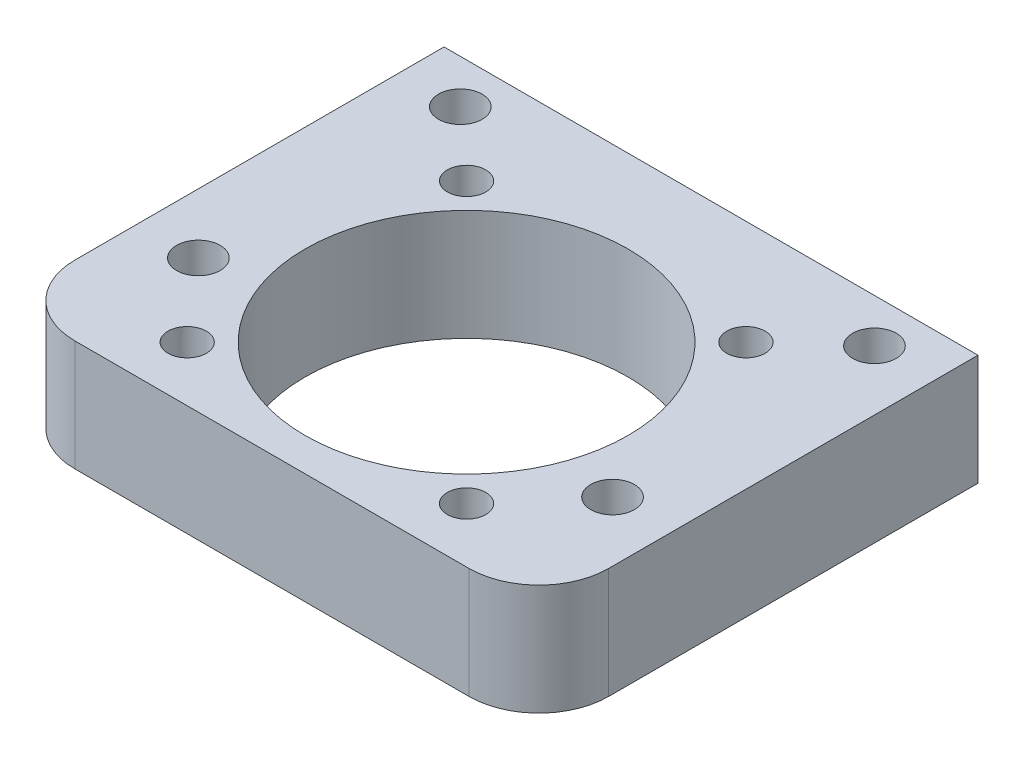
SolidWorks part; units mm, degrees
ref_plane "Front" through (0, 0, 0) normal (0, 0, 1) x (1, 0, 0)
ref_plane "Top" through (0, 0, 0) normal (0, 1, 0) x (1, 0, 0)
ref_plane "Right" through (0, 0, 0) normal (1, 0, 0) x (0, 0, -1)
ref_plane "Plane1" through (0, 6.35, 0) normal (0, 1, 0) x (1, 0, 0)
sketch "Sketch1" plane through (0, 6.35, 0) normal (0, 1, 0) x (1, 0, 0)
  line L0 (15.289, -7.15) -> (15.289, 14)
  line L1 (15.289, 14) -> (-15.289, 14)
  line L2 (-15.289, 14) -> (-15.289, -7.15)
  line L3 (-11.289, -11.15) -> (11.289, -11.15)
  arc A0 (11.289, -11.15) -> (15.289, -7.15) centre (11.289, -7.15) ccw
  arc A1 (-15.289, -7.15) -> (-11.289, -11.15) centre (-11.289, -7.15) ccw
extrude "Boss-Extrude1" add sketch "Sketch1" against normal blind 6.35
hole_wizard "Ø2.2 (2.2) Diameter Hole1" positions "Sketch3" profile "Sketch2" hole size "Ø2.2" standard "ANSI Metric"
sketch "Sketch3" plane through (0, 0, 0) normal (0, -1, 0) x (-1, 0, 0)
  point P0 (-8, -8)
sketch "Sketch2" plane through (8, 0, 8) normal (1, 0, 0) x (0, 0, -1)
  line L0 (0, 0) -> (0, 6.35)
  line L1 (0, 6.35) -> (1.1, 6.35)
  line L2 (1.1, 6.35) -> (1.1, 0)
  line L5 (1.1, 0) -> (0, 0)
  line L11 (0, -6.35) -> (0, 107.95) construction
  dimension "Thru Hole Dia." = 2.2
  dimension "Thru Hole Depth" = 6.35
hole_wizard "Ø2.2 (2.2) Diameter Hole2" positions "Sketch5" profile "Sketch4" hole size "Ø2.2" standard "ANSI Metric"
sketch "Sketch5" plane through (0, 0, 0) normal (0, -1, 0) x (-1, 0, 0)
  point P0 (8, 8)
sketch "Sketch4" plane through (-8, 0, -8) normal (1, 0, 0) x (0, 0, -1)
  line L0 (0, 0) -> (0, 6.35)
  line L1 (0, 6.35) -> (1.1, 6.35)
  line L2 (1.1, 6.35) -> (1.1, 0)
  line L5 (1.1, 0) -> (0, 0)
  line L11 (0, -6.35) -> (0, 107.95) construction
  dimension "Thru Hole Dia." = 2.2
  dimension "Thru Hole Depth" = 6.35
hole_wizard "Ø2.2 (2.2) Diameter Hole3" positions "Sketch7" profile "Sketch6" hole size "Ø2.2" standard "ANSI Metric"
sketch "Sketch7" plane through (0, 0, 0) normal (0, -1, 0) x (-1, 0, 0)
  point P0 (-8, 8)
sketch "Sketch6" plane through (8, 0, -8) normal (1, 0, 0) x (0, 0, -1)
  line L0 (0, 0) -> (0, 6.35)
  line L1 (0, 6.35) -> (1.1, 6.35)
  line L2 (1.1, 6.35) -> (1.1, 0)
  line L5 (1.1, 0) -> (0, 0)
  line L11 (0, -6.35) -> (0, 107.95) construction
  dimension "Thru Hole Dia." = 2.2
  dimension "Thru Hole Depth" = 6.35
hole_wizard "Ø2.2 (2.2) Diameter Hole4" positions "Sketch19" profile "Sketch18" hole size "Ø2.2" standard "ANSI Metric"
sketch "Sketch19" plane through (0, 6.35, 0) normal (0, 1, 0) x (1, 0, 0)
  point P0 (-8, -8)
sketch "Sketch18" plane through (-8, 6.35, 8) normal (1, 0, 0) x (0, 0, 1)
  line L0 (0, 0) -> (0, 6.35)
  line L1 (0, 6.35) -> (1.1, 6.35)
  line L2 (1.1, 6.35) -> (1.1, 0)
  line L5 (1.1, 0) -> (0, 0)
  line L11 (0, -6.35) -> (0, 107.95) construction
  dimension "Thru Hole Dia." = 2.2
  dimension "Thru Hole Depth" = 6.35
hole_wizard "Ø18.5 (18.5) Diameter Hole1" positions "Sketch9" profile "Sketch8" hole size "Ø18.5" standard "ANSI Metric"
sketch "Sketch9" plane through (0, 0, 0) normal (0, -1, 0) x (-1, 0, 0)
  point P0 (0, 0)
sketch "Sketch8" plane through (0, 0, 0) normal (1, 0, 0) x (0, 0, -1)
  line L0 (0, 0) -> (0, 6.35)
  line L1 (0, 6.35) -> (9.25, 6.35)
  line L2 (9.25, 6.35) -> (9.25, 0)
  line L5 (9.25, 0) -> (0, 0)
  line L11 (0, -6.35) -> (0, 107.95) construction
  dimension "Thru Hole Dia." = 18.5
  dimension "Thru Hole Depth" = 6.35
hole_wizard "M3 Tapped Hole1" positions "Sketch11" profile "Sketch10" tap size "M3" standard "ISO" end condition through all
sketch "Sketch11" plane through (0, 0, 0) normal (0, -1, 0) x (-1, 0, 0)
  point P0 (11.8586, 11.5)
sketch "Sketch10" plane through (-11.8586, 0, -11.5) normal (1, 0, 0) x (0, 0, -1)
  line L0 (0, 0) -> (0, 6.35)
  line L1 (0, 6.35) -> (1.25, 6.35)
  line L2 (1.25, 6.35) -> (1.25, 0)
  line L5 (1.25, 0) -> (0, 0)
  line L11 (0, -6.35) -> (0, 107.95) construction
  dimension "Thru Tap Drill Dia." = 2.5
  dimension "Thru Tap Drill Depth" = 6.35
cosmetic thread "Hole Thread1"
hole_wizard "M3 Tapped Hole2" positions "Sketch13" profile "Sketch12" tap size "M3" standard "ISO" end condition through all
sketch "Sketch13" plane through (0, 0, 0) normal (0, -1, 0) x (-1, 0, 0)
  point P0 (11.8596, -3.5)
sketch "Sketch12" plane through (-11.8596, 0, 3.5) normal (1, 0, 0) x (0, 0, -1)
  line L0 (0, 0) -> (0, 6.35)
  line L1 (0, 6.35) -> (1.25, 6.35)
  line L2 (1.25, 6.35) -> (1.25, 0)
  line L5 (1.25, 0) -> (0, 0)
  line L11 (0, -6.35) -> (0, 107.95) construction
  dimension "Thru Tap Drill Dia." = 2.5
  dimension "Thru Tap Drill Depth" = 6.35
cosmetic thread "Hole Thread2" parameters "D2"=3
hole_wizard "M3 Tapped Hole3" positions "Sketch15" profile "Sketch14" tap size "M3" standard "ISO" end condition through all
sketch "Sketch15" plane through (0, 0, 0) normal (0, -1, 0) x (-1, 0, 0)
  point P0 (-11.8586, 11.5)
sketch "Sketch14" plane through (11.8586, 0, -11.5) normal (1, 0, 0) x (0, 0, -1)
  line L0 (0, 0) -> (0, 6.35)
  line L1 (0, 6.35) -> (1.25, 6.35)
  line L2 (1.25, 6.35) -> (1.25, 0)
  line L5 (1.25, 0) -> (0, 0)
  line L11 (0, -6.35) -> (0, 107.95) construction
  dimension "Thru Tap Drill Dia." = 2.5
  dimension "Thru Tap Drill Depth" = 6.35
cosmetic thread "Hole Thread3" parameters "D2"=3
hole_wizard "M3 Tapped Hole4" positions "Sketch17" profile "Sketch16" tap size "M3" standard "ISO" end condition through all
sketch "Sketch17" plane through (0, 0, 0) normal (0, -1, 0) x (-1, 0, 0)
  point P0 (-11.8596, -3.5)
sketch "Sketch16" plane through (11.8596, 0, 3.5) normal (1, 0, 0) x (0, 0, -1)
  line L0 (0, 0) -> (0, 6.35)
  line L1 (0, 6.35) -> (1.25, 6.35)
  line L2 (1.25, 6.35) -> (1.25, 0)
  line L5 (1.25, 0) -> (0, 0)
  line L11 (0, -6.35) -> (0, 107.95) construction
  dimension "Thru Tap Drill Dia." = 2.5
  dimension "Thru Tap Drill Depth" = 6.35
cosmetic thread "Hole Thread4" parameters "D2"=3
